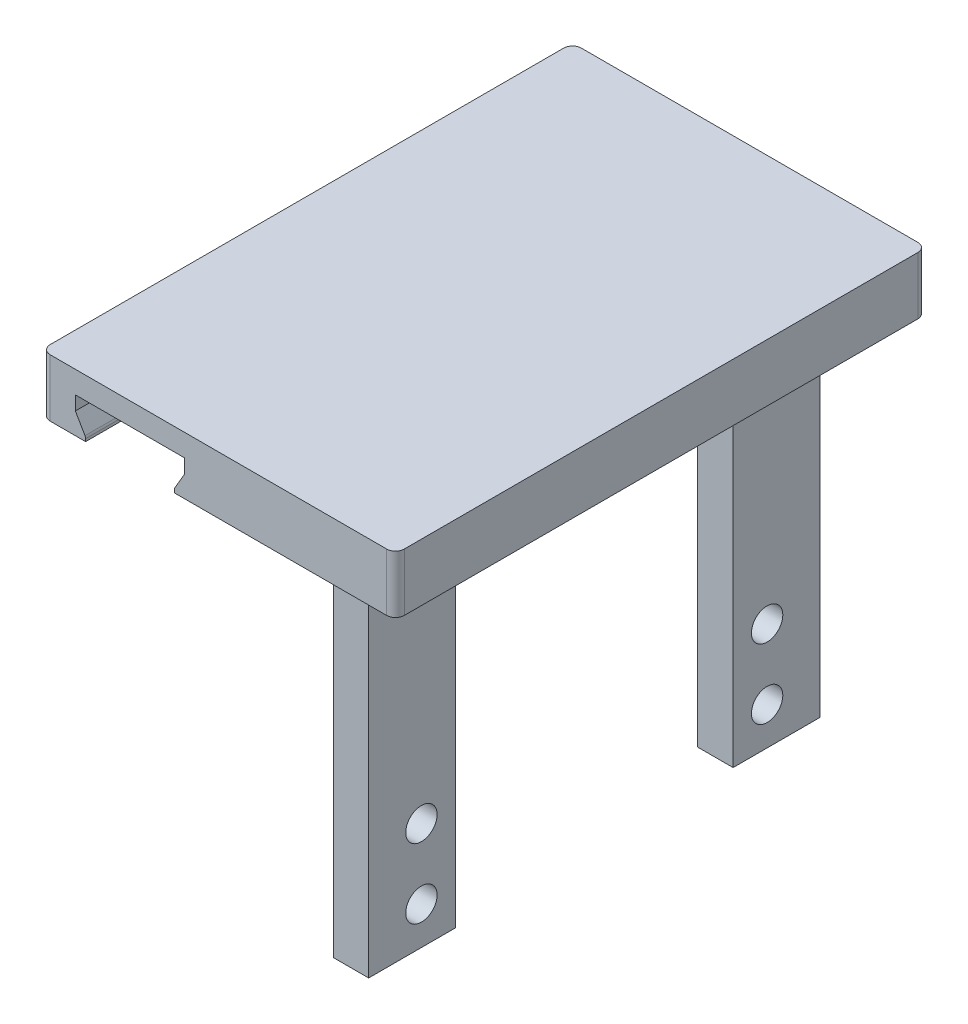
SolidWorks part; units mm, degrees
ref_plane "Front Plane" through (0, 0, 0) normal (0, 0, 1) x (1, 0, 0)
ref_plane "Top Plane" through (0, 0, 0) normal (0, 1, 0) x (1, 0, 0)
ref_plane "Right Plane" through (0, 0, 0) normal (1, 0, 0) x (0, 0, -1)
sketch "Sketch2" plane through (0, 0, 0) normal (0, 1, 0) x (1, 0, 0)
  line L0 (0, 0) -> (0, -76.2)
  line L1 (0, -76.2) -> (50.8, -76.2)
  line L2 (50.8, -76.2) -> (50.8, 0)
  line L3 (50.8, 0) -> (0, 0)
  line L4 (0, -38.1) -> (6.35, -38.1)
  line L5 (6.35, -38.1) -> (19.0754, -38.1)
  line L6 (19.0754, -38.1) -> (36.139, -38.1)
  line L7 (36.139, -38.1) -> (36.139, -62.844)
  line L8 (36.139, -62.844) -> (41.219, -62.844)
  line L9 (41.219, -58.018) -> (36.139, -58.018)
  line L10 (36.139, -38.1) -> (36.139, -13.356)
  line L11 (36.139, -62.844) -> (36.139, -70.464)
  line L12 (36.139, -70.464) -> (41.219, -70.464)
  line L13 (41.219, -70.464) -> (41.219, -62.844)
  line L14 (36.139, -13.356) -> (41.219, -13.356)
  line L15 (41.219, -62.844) -> (41.219, -58.018)
  line L16 (41.219, -13.356) -> (41.219, -18.182)
  line L17 (41.219, -18.182) -> (36.139, -18.182)
  line L18 (41.219, -13.356) -> (41.219, -5.736)
  line L19 (36.139, -13.356) -> (36.139, -5.736)
  line L20 (36.139, -5.736) -> (41.219, -5.736)
  line L21 (6.35, -38.1) -> (6.35, 0)
  line L22 (6.35, -76.2) -> (6.35, -38.1)
  line L23 (19.0754, -38.1) -> (19.0754, -76.2)
  line L24 (19.0754, -38.1) -> (19.0754, 0)
  dimension "D1" = 76.2
  dimension "D2" = 50.8
  dimension "D3" = 6.35
  dimension "D4" = 12.7254
  dimension "D5" = 24.744
  dimension "D6" = 7.62
  dimension "D7" = 24.744
  dimension "D8" = 5.08
  dimension "D9" = 4.826
  dimension "D10" = 5.08
  dimension "D11" = 4.826
  dimension "D12" = 7.62
  dimension "D13" = 17.0636
extrude "Boss-Extrude1" add sketch "Sketch2" along normal blind 3.175 contours L4 L21 L3 L0 | L5 L24 L3 L21 | L24 L10 L19 L20 L18 L16 L17 L9 L15 L13 L12 L11 L7 L23 L1 L2 L3 | L1 L22 L4 L0 | L23 L5 L22 L1 | L8 L15 L9 L7 | L12 L13 L8 L11 | L20 L19 L14 L18 | L17 L16 L14 L10 region at (3.175, 0, 19.05) region at (3.175, 0, 57.15) region at (12.7127, 0, 19.05) region at (12.7127, 0, 57.15) region at (38.679, 0, 15.769) region at (38.679, 0, 60.431) region at (34.9377, 0, 0.8254) region at (38.679, 0, 66.654) region at (38.679, 0, 9.546)
extrude "Boss-Extrude2" add sketch "Sketch2<5>" against normal blind 5.08 contours L1 L22 L4 L0 | L24 L10 L19 L20 L18 L16 L17 L9 L15 L13 L12 L11 L7 L23 L1 L2 L3 | L4 L21 L3 L0 region at (3.175, 0, 19.05) region at (3.175, 0, 57.15) region at (34.9377, 0, 0.8254)
sketch "Sketch2<5>" plane through (0, 0, 0) normal (0, 1, 0) x (1, 0, 0) same geometry as "Sketch2"
extrude "Boss-Extrude3" add sketch "Sketch2<6>" against normal blind 57.15 contours L17 L16 L14 L10 | L20 L19 L14 L18 | L12 L13 L8 L11 | L8 L15 L9 L7 region at (38.679, 0, 15.769) region at (38.679, 0, 60.431) region at (38.679, 0, 66.654) region at (38.679, 0, 9.546)
sketch "Sketch2<6>" plane through (0, 0, 0) normal (0, 1, 0) x (1, 0, 0) same geometry as "Sketch2"
sketch "Sketch4" plane through (36.139, 0, 0) normal (-1, 0, 0) x (0, 0, 1)
  line L0 (18.182, -57.15) -> (5.736, -57.15) construction
  line L2 (13.3052, -46.7433) -> (13.3052, -41.7433)
  line L3 (13.3052, -46.7433) -> (13.3052, -51.7433)
  line L5 (58.018, -57.15) -> (70.464, -57.15) construction
  line L6 (62.8948, -46.7433) -> (62.8948, -41.7433)
  line L7 (62.8948, -46.7433) -> (62.8948, -51.7433)
  line L8 (62.8948, -51.7433) -> (58.018, -51.7433)
  line L9 (58.018, -57.15) -> (58.018, -5.08) construction
  line L10 (13.3052, -51.7433) -> (18.182, -51.7433)
  line L11 (18.182, -57.15) -> (18.182, -5.08) construction
  circle A0 centre (13.3052, -41.7433) radius 2.25
  circle A1 centre (13.3052, -51.7433) radius 2.25
  circle A2 centre (62.8948, -41.7433) radius 2.25
  circle A3 centre (62.8948, -51.7433) radius 2.25
  dimension "D2" = 4.5
  dimension "D4" = 4.5
  dimension "D5" = 4.5
  dimension "D9" = 4.5
  dimension "D3" = 5
  dimension "D6" = 4.8768
  dimension "D7" = 5
  dimension "D8" = 5
  dimension "D10" = 5.4067
  dimension "D11" = 5.4067
  dimension "D12" = 4.8768
extrude "Cut-Extrude1" cut sketch "Sketch4" against normal blind 50.8 contours A2 | A3 | L7 A3 L8 | A1 | A0 region at (36.139, -40.1973, 61.3488) region at (36.139, -52.0616, 63.2131) region at (36.139, -50.7884, 61.9399)
fillet "Fillet1" radius 1.27 12 edges at (0, -0.9525, 0) (0, -0.9525, 76.2) (50.8, -0.9525, 76.2) (50.8, -0.9525, 0) (38.679, -5.08, 70.464) (36.139, -5.08, 64.241) (38.679, -5.08, 58.018) (41.219, -5.08, 11.959) (36.139, -5.08, 11.959) (38.679, -5.08, 5.736) (41.219, -5.08, 64.241) (38.679, -5.08, 18.182)
sketch "Sketch5" plane through (0, 0, 0) normal (0, 0, -1) x (-1, 0, 0)
  line L0 (-19.0754, 0) -> (-20.5486, 0)
  line L1 (27.94, 0) -> (-27.94, 0) construction
  line L2 (-20.5486, 0) -> (-20.5486, -2.0066)
  line L3 (-19.0754, -2.0066) -> (-19.0754, -5.08)
  line L4 (-19.0754, -5.08) -> (-19.0754, 0) construction
  line L5 (-20.5486, -2.0066) -> (-19.0754, -2.0066)
  line L6 (-20.5486, -2.0066) -> (-19.0754, -4.532)
  line L7 (-19.0754, 0) -> (-19.0754, -2.0066)
  line L8 (-6.35, 0) -> (-4.8768, 0)
  line L10 (-4.8768, 0) -> (-4.8768, -2.0066)
  line L11 (-4.8768, -2.0066) -> (-6.35, -2.0066)
  line L12 (-6.35, -5.08) -> (-6.35, 0) construction
  line L13 (-6.35, -2.0066) -> (-6.35, -4.532)
  line L14 (-6.35, -4.532) -> (-4.8768, -2.0066)
  line M11 (-19.0754, -5.08) -> (-19.0754, 0)
  line M13 (-6.35, 0) -> (-6.35, -5.08)
  dimension "D1" = 1.4732
  dimension "D2" = 2.0066
  dimension "D3" = 1.4732
  dimension "D4" = 2.0066
extrude "Cut-Extrude2" cut sketch "Sketch5" against normal blind 101.6 contours L2 L5 L0 M11 | L5 L6 L3 | L11 L10 M13 | L14 L11 M13 region at (19.812, -1.0033, 0) region at (19.5665, -2.8484, 0) region at (5.6134, -1.0033, 0) region at (5.8589, -2.8484, 0)
fillet "Fillet2" radius 0.635 2 edges at (19.0754, -4.532, 38.1) (6.35, -4.532, 38.1)
